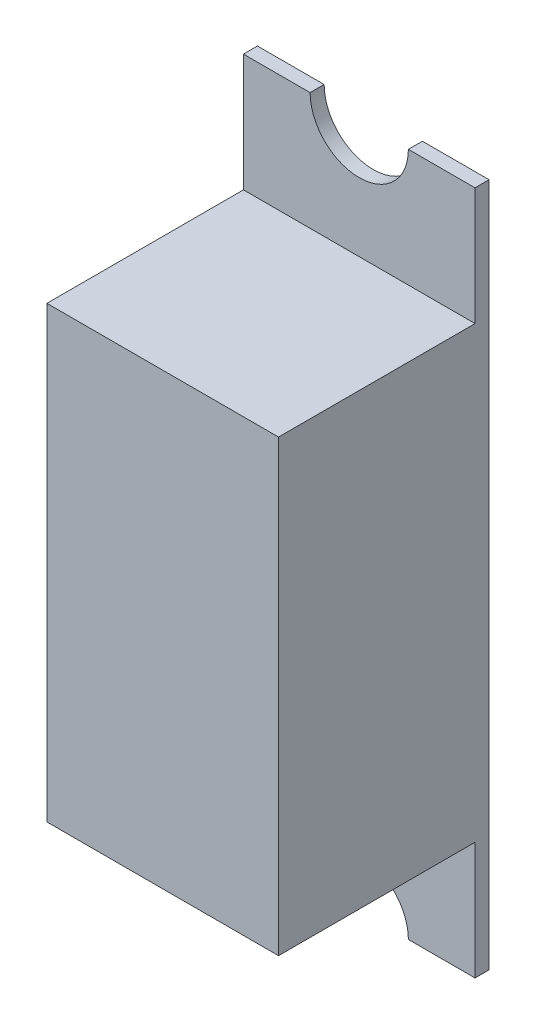
SolidWorks part; units mm, degrees
ref_plane "Plan de face" through (0, 0, 0) normal (0, 0, 1) x (1, 0, 0)
ref_plane "Plan de dessus" through (0, 0, 0) normal (0, 1, 0) x (1, 0, 0)
ref_plane "Plan de droite" through (0, 0, 0) normal (1, 0, 0) x (0, 0, -1)
sketch "Esquisse1" plane through (0, 0, 0) normal (0, 0, 1) x (1, 0, 0)
  line L1 (0, 0) -> (-6.6, 0)
  line L2 (0, 0) -> (0, -12.8)
  line L3 (0, -12.8) -> (-6.6, -12.8)
  line L4 (-6.6, 0) -> (-6.6, -12.8)
  dimension "D1" = 12.8
  dimension "D2" = 6.6
extrude "Boss.-Extru.1" add sketch "Esquisse1" along normal blind 5.6
sketch "Esquisse2" plane through (0, 0, 0) normal (0, 0, -1) x (-1, 0, 0)
  line L0 (6.6, 0) -> (6.6, -12.8) construction
  line L1 (0, 3.35) -> (6.6, 3.35)
  line L2 (0, 3.35) -> (0, -16.15)
  line L3 (0, -16.15) -> (6.6, -16.15)
  line L4 (6.6, 3.35) -> (6.6, -16.15)
  line L5 (0, -12.8) -> (0, 0) construction
  line L7 (6.6, -12.8) -> (0, -12.8) construction
  line L9 (0, 0) -> (6.6, 0) construction
  line L11 (1.9, 3.35) -> (4.7, 3.35)
  line L12 (1.9, 3.35) -> (1.9, -16.15)
  line L13 (1.9, -16.15) -> (4.7, -16.15)
  line L14 (4.7, 3.35) -> (4.7, -16.15)
  arc A0 (1.9, 3.35) -> (4.7, 3.35) centre (3.3, 3.35) ccw
  arc A1 (1.9, -16.15) -> (4.7, -16.15) centre (3.3, -16.15) cw
  point P16 (3.3, 3.35)
  line M5 (0, 0) -> (0, -12.8)
  line M6 (0, -12.8) -> (6.6, -12.8)
  line M7 (6.6, -12.8) -> (6.6, 0)
  line M8 (6.6, 0) -> (0, 0)
  dimension "D1" = 0
  dimension "D2" = 0
  dimension "D3" = 19.5
  dimension "D4" = 3.35
  dimension "D5" = 3.35
  dimension "D6" = 2.8
  dimension "D7" = 1.4
extrude "Boss.-Extru.2" add sketch "Esquisse2" along normal blind 0.4 contours L12 M8 M5 M6 | L14 L12 M8 M6 | L14 M8 M6 M7 | L12 L2 L3 M6 | L12 A1 L14 M6 | L14 L3 L4 M6 | L12 L1 L2 M8 | A0 L12 L14 M8 | L1 L14 L4 M8 region at (-0.95, 1.675, 0) region at (-3.3, 1.1469, 0) region at (-0.95, -6.4, 0) region at (-5.65, 1.675, 0) region at (-3.3, -6.4, 0) region at (-0.95, -14.475, 0) region at (-5.65, -6.4, 0) region at (-3.3, -13.9469, 0) region at (-5.65, -14.475, 0)
